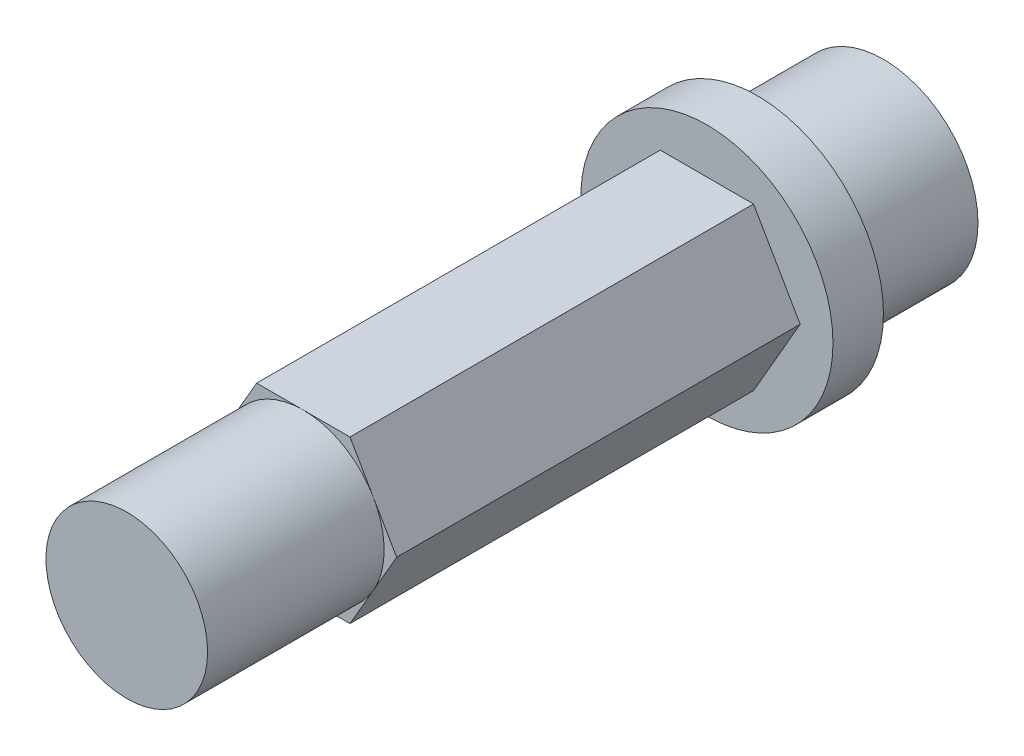
SolidWorks part; units mm, degrees
ref_plane "Front Plane" through (0, 0, 0) normal (0, 0, 1) x (1, 0, 0)
ref_plane "Top Plane" through (0, 0, 0) normal (0, 1, 0) x (1, 0, 0)
ref_plane "Right Plane" through (0, 0, 0) normal (1, 0, 0) x (0, 0, -1)
sketch "Sketch1" plane through (0, 0, 0) normal (0, 0, 1) x (1, 0, 0)
  circle A0 centre (0, 0) radius 3.75
  dimension "D1" = 7.5
extrude "Boss-Extrude1" add sketch "Sketch1" along normal blind 5
sketch "Sketch2" plane through (0, 0, 5) normal (0, 0, 1) x (1, 0, 0)
  circle A0 centre (0, 0) radius 5
  dimension "D1" = 10
extrude "Boss-Extrude2" add sketch "Sketch2" along normal blind 2
sketch "Sketch3" plane through (0, 0, 7) normal (0, 0, 1) x (1, 0, 0)
  line L7 (3.7, 0) -> (1.85, 3.2043)
  line L8 (1.85, 3.2043) -> (-1.85, 3.2043)
  line L9 (-1.85, 3.2043) -> (-3.7, 0)
  line L10 (-3.7, 0) -> (-1.85, -3.2043)
  line L11 (-1.85, -3.2043) -> (1.85, -3.2043)
  line L12 (1.85, -3.2043) -> (3.7, 0)
  circle A0 centre (0, 0) radius 3.7 construction
  circle A1 centre (0, 0) radius 3.2043 construction
  dimension "D1" = 7.4
extrude "Boss-Extrude3" add sketch "Sketch3" along normal blind 16
sketch "Sketch4" plane through (0, 0, 23) normal (0, 0, 1) x (1, 0, 0)
  line L2 (-1.85, 3.2043) -> (-3.7, 0) construction
  circle A0 centre (0, 0) radius 3.2043
extrude "Boss-Extrude4" add sketch "Sketch4" along normal blind 7
equation "\"gear_length\"=16"
equation "\"D1@Boss-Extrude3\"=\"gear_length\""
